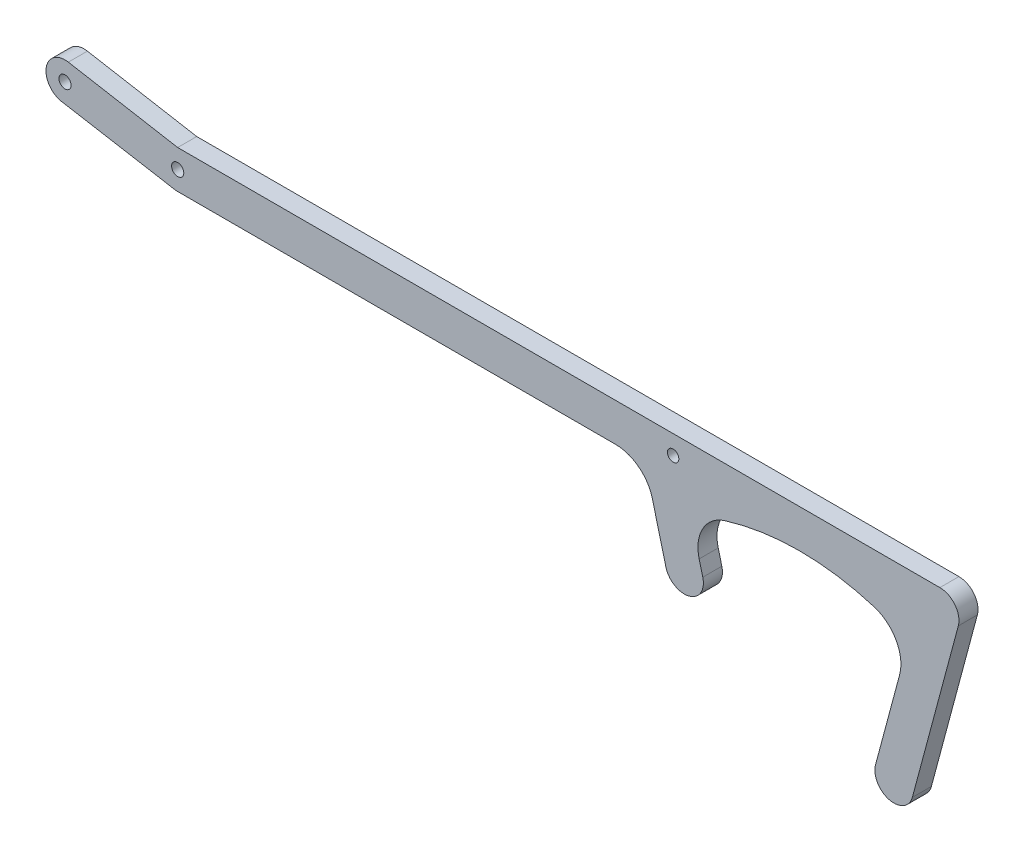
SolidWorks part; units mm, degrees
ref_plane "Front Plane" through (0, 0, 0) normal (0, 0, 1) x (1, 0, 0)
ref_plane "Top Plane" through (0, 0, 0) normal (0, 1, 0) x (1, 0, 0)
ref_plane "Right Plane" through (0, 0, 0) normal (1, 0, 0) x (0, 0, -1)
sketch "Sketch1" plane through (0, 0, 0) normal (0, 0, 1) x (1, 0, 0)
  line L0 (0, 0) -> (254, 0) construction
  line L1 (0, 6.35) -> (254, 6.35)
  line L2 (0, -6.35) -> (155.7202, -6.35)
  line L3 (260.1336, -1.6435) -> (244.8203, -58.7935)
  line L4 (232.5531, -55.5065) -> (243.5126, -14.605)
  line L6 (162.6883, -33.3375) -> (155.7202, -6.35)
  line L7 (174.9851, -30.1625) -> (170.9681, -14.605)
  line L8 (0, 0) -> (-37.5378, 6.521) construction
  line L10 (0, 6.35) -> (-36.4351, 12.7745)
  line L11 (-38.6246, 0.2647) -> (-1.0868, -6.2563)
  circle A0 centre (0, 0) radius 2.032
  arc A2 (260.1336, -1.6435) -> (254, 6.35) centre (254, 0) ccw
  arc A3 (232.5531, -55.5065) -> (244.8203, -58.7935) centre (238.6867, -57.15) ccw
  arc A5 (162.6883, -33.3375) -> (174.9851, -30.1625) centre (168.8367, -31.75) ccw
  arc A6 (170.9681, -14.605) -> (243.5126, -14.605) centre (207.2404, -90.8741) cw
  circle A7 centre (165.1, 0) radius 1.905
  arc A9 (-36.4351, 12.7745) -> (-38.6246, 0.2647) centre (-37.5378, 6.521) ccw
  circle A10 centre (-37.5378, 6.521) radius 2.032
  arc A12 (0, -6.35) -> (-1.0868, -6.2563) centre (0, 0) cw
  point P7 (0, 0)
  point P21 (-40.0132, 7.8061)
  point P28 (-40.0132, 7.8061)
  point P29 (0, 0)
  point P30 (-36.9622, 6.35)
  dimension "D1" = 31.75
  dimension "D3" = 6.35
  dimension "D5" = 6.35
  dimension "D6" = 6.35
  dimension "D11" = 4.064
  dimension "D14" = 17.145
  dimension "D10" = 75
  dimension "D13" = 84.455
  dimension "D15" = 3.81
  dimension "D19" = 6.35
  dimension "D21" = 4.064
  dimension "D17" = 6.35
  dimension "D4" = 12.7
  dimension "D7" = 254
  dimension "D8" = 57.15
  dimension "D9" = 69.85
  dimension "D12" = 26.9875
  dimension "D16" = 165.1
  dimension "D18" = 38.1
  dimension "D20" = 170
extrude "Boss-Extrude1" add sketch "Sketch1" along normal mid plane 6.35
fillet "Fillet1" radius 12.7 1 edges at (155.7202, -6.35, 0)
fillet "Fillet2" radius 12.7 2 edges at (243.5126, -14.605, 0) (170.9681, -14.605, 0)
